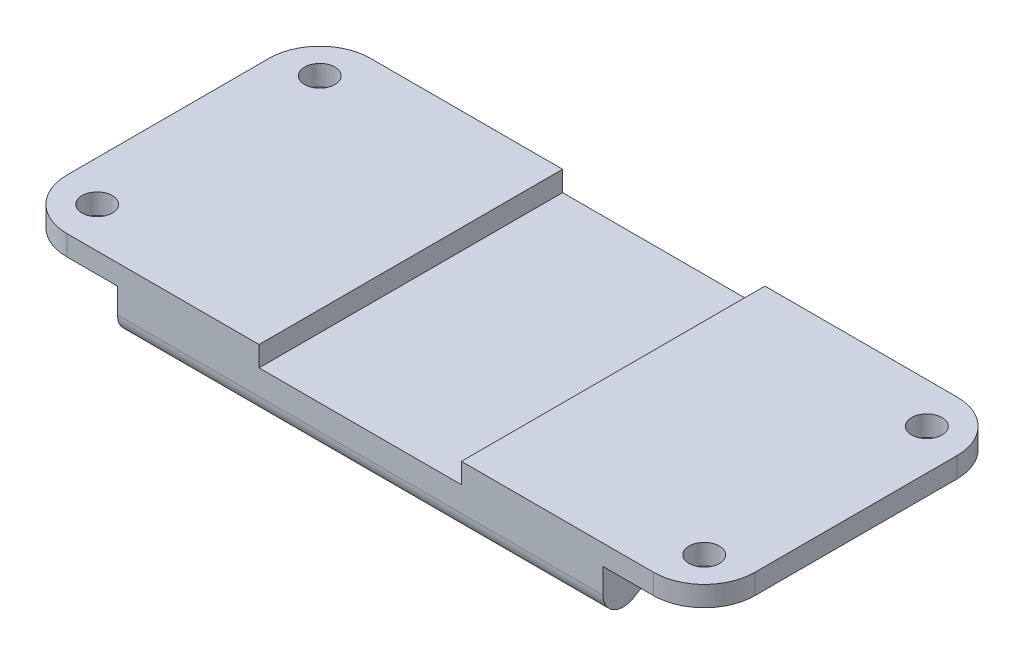
SolidWorks part; units mm, degrees
material "PEI"
ref_plane "Front Plane" through (0, 0, 0) normal (0, 0, 1) x (1, 0, 0)
ref_plane "Top Plane" through (0, 0, 0) normal (0, 1, 0) x (1, 0, 0)
ref_plane "Right Plane" through (0, 0, 0) normal (1, 0, 0) x (0, 0, -1)
sketch "Sketch1" plane through (0, 0, 0) normal (0, 1, 0) x (1, 0, 0)
  line L1 (24, -15) -> (-24, -15)
  line L2 (24, -15) -> (24, 15)
  line L3 (24, 15) -> (-24, 15)
  line L4 (-24, -15) -> (-24, 15)
  line L5 (24, -15) -> (-24, 15) construction
  line L6 (24, 15) -> (-24, -15) construction
  point P0 (0, 0)
  dimension "D1" = 30
  dimension "D2" = 48
extrude "Boss-Extrude1" add sketch "Sketch1" against normal blind 8
sketch "Sketch2" plane through (24, 0, 0) normal (1, 0, 0) x (0, 0, -1)
  line L0 (-15, -8) -> (-10, -5)
  line L1 (-10, -5) -> (10, -5)
  line L2 (0, -5) -> (0, -8)
  line L3 (15, -8) -> (10, -5)
  line L4 (15, 0) -> (-15, 0)
  line L5 (-15, 0) -> (-15, -8)
  line L6 (-15, -8) -> (15, -8)
  line L7 (15, -8) -> (15, 0)
  line L8 (15, 0) -> (-15, 0)
  line L9 (-15, 0) -> (-15, -8)
  line L10 (-15, -8) -> (15, -8)
  line L11 (15, -8) -> (15, 0)
  line M7 (-15, -8) -> (15, -8)
  dimension "D2" = 5
  dimension "D3" = 3
  dimension "D1" = 0
extrude "Cut-Extrude1" cut sketch "Sketch2" against normal through all and the other way through all contours L2 L1 L0 M7 | L3 L1 L2 M7 region at (24, -6.6, 6.3333) region at (24, -6.6, -6.3333)
fillet "Fillet1" radius 2 4 edges at (0, -5, 10) (0, -5, -10) (0, -8, -15) (0, -8, 15)
sketch "Sketch3" plane through (0, 0, 15) normal (0, 0, 1) x (1, 0, 0)
  line L0 (-24, 0) -> (24, 0) construction
  line L1 (-10, 2) -> (10, 2)
  line L2 (-10, 2) -> (-10, -2)
  line L3 (-10, -2) -> (10, -2)
  line L4 (-24, 0) -> (-24, -4.4676)
  line L5 (-24, -4.4676) -> (24, -4.4676)
  line L6 (24, -4.4676) -> (24, 0)
  line L7 (24, 0) -> (-24, 0)
  line L8 (-24, 0) -> (-24, -4.4676)
  line L9 (-24, -4.4676) -> (24, -4.4676)
  line L10 (24, -4.4676) -> (24, 0)
  line L11 (24, 0) -> (-24, 0)
  line L12 (10, 2) -> (10, -2)
  line L13 (-10, 2) -> (10, -2) construction
  line L14 (-10, -2) -> (10, 2) construction
  line L15 (0, 0) -> (0, -4.4676)
  point P2 (0, 0)
  point P18 (0, 0)
  line M10 (24, 0) -> (-24, 0)
  dimension "D2" = 20
  dimension "D3" = 4
  dimension "D1" = 0
sketch "Sketch5" plane through (-24, 0, 0) normal (-1, 0, 0) x (0, 0, 1)
  line L1 (-15, 0) -> (15, 0)
  line L2 (-15, 0) -> (-15, -2)
  line L3 (-15, -2) -> (15, -2)
  line L4 (15, 0) -> (15, -2)
  line L6 (-15, 0) -> (-15, -4.4676)
  line L7 (-11.971, -6.1826) -> (-10.475, -5.285)
  line L8 (-9.446, -5) -> (9.446, -5)
  line L9 (10.475, -5.285) -> (11.971, -6.1826)
  line L10 (15, -4.4676) -> (15, 0)
  line L11 (15, 0) -> (-15, 0)
  line L12 (-15, 0) -> (-15, -4.4676)
  line L13 (-11.971, -6.1826) -> (-10.475, -5.285)
  line L14 (-9.446, -5) -> (9.446, -5)
  line L15 (10.475, -5.285) -> (11.971, -6.1826)
  line L16 (15, -4.4676) -> (15, 0)
  line L17 (15, 0) -> (-15, 0)
  arc A4 (-15, -4.4676) -> (-11.971, -6.1826) centre (-13, -4.4676) ccw
  arc A5 (-9.446, -5) -> (-10.475, -5.285) centre (-9.446, -7) ccw
  arc A6 (10.475, -5.285) -> (9.446, -5) centre (9.446, -7) ccw
  arc A7 (11.971, -6.1826) -> (15, -4.4676) centre (13, -4.4676) ccw
  arc A8 (-15, -4.4676) -> (-11.971, -6.1826) centre (-13, -4.4676) ccw
  arc A9 (-9.446, -5) -> (-10.475, -5.285) centre (-9.446, -7) ccw
  arc A10 (10.475, -5.285) -> (9.446, -5) centre (9.446, -7) ccw
  arc A11 (11.971, -6.1826) -> (15, -4.4676) centre (13, -4.4676) ccw
  line M13 (-15, 0) -> (-15, -4.4676)
  line M21 (15, -4.4676) -> (15, 0)
  line M22 (15, 0) -> (-15, 0)
  dimension "D2" = 2
  dimension "D1" = 0
extrude "Boss-Extrude2" add sketch "Sketch5" along normal blind 10 contours L3 M13 M21 M22 region at (-24, -1, 0)
mirror "Mirror1" about plane through (0, 0, 0) normal (1, 0, 0) of "Boss-Extrude2"
sketch "Sketch6" plane through (0, 0, 0) normal (0, 1, 0) x (1, 0, 0)
  line L0 (0, 0) -> (-30, 0)
  line L1 (-30, 0) -> (-30, 11)
  line L2 (0, 0) -> (0, 15)
  line L4 (34, 15) -> (-34, 15)
  line L5 (-34, 15) -> (-34, -15)
  line L6 (-34, -15) -> (34, -15)
  line L7 (34, -15) -> (34, 15)
  line L8 (34, 15) -> (-34, 15)
  line L9 (-34, 15) -> (-34, -15)
  line L10 (-34, -15) -> (34, -15)
  line L11 (34, -15) -> (34, 15)
  circle A0 centre (-30, 11) radius 1.5
  circle A1 centre (-30, -11) radius 1.5
  circle A2 centre (30, -11) radius 1.5
  circle A3 centre (30, 11) radius 1.5
  dimension "D4" = 3
  dimension "D2" = 11
  dimension "D3" = 30
  dimension "D1" = 0
extrude "Cut-Extrude2" cut sketch "Sketch6" against normal blind 10 contours A0 | A1 | A3 | A2 region at (-31.0307, 0, -12.0307) region at (-30, 0, 11) region at (30, 0, 11) region at (30, 0, -11)
extrude "Cut-Extrude3" cut sketch "Sketch3" against normal through all contours L11 L15 L3 L12 | L15 L2 L3 M10 region at (-5, -1, 15) region at (5, -1, 15)
fillet "Fillet3" radius 5 4 edges at (34, -1, 15) (34, -1, -15) (-34, -1, -15) (-34, -1, 15)
